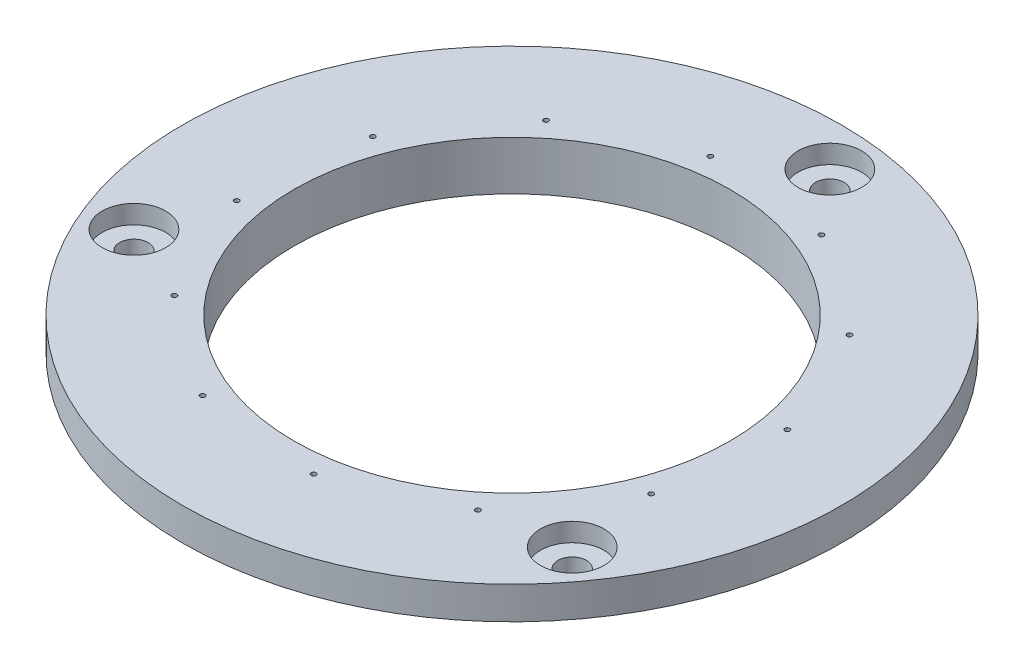
SolidWorks part; units mm, degrees
ref_plane "Front Plane" through (0, 0, 0) normal (0, 0, 1) x (1, 0, 0)
ref_plane "Top Plane" through (0, 0, 0) normal (0, 1, 0) x (1, 0, 0)
ref_plane "Right Plane" through (0, 0, 0) normal (1, 0, 0) x (0, 0, -1)
sketch "Sketch2" plane through (0, 0, 0) normal (0, 1, 0) x (1, 0, 0)
  circle A0 centre (0, 0) radius 63.5
  circle A1 centre (0, 0) radius 42
  dimension "D1" = 127
  dimension "D2" = 84
extrude "Boss-Extrude1" add sketch "Sketch2" along normal blind 9.45
sketch "Sketch15" plane through (0, 9.45, 0) normal (0, 1, 0) x (1, 0, 0)
  line L1 (6.244, 55) -> (-50.7534, -22.0925)
  line L2 (-50.7534, -22.0925) -> (44.5094, -32.9075)
  line L3 (44.5094, -32.9075) -> (6.244, 55)
  circle A0 centre (0, 0) radius 27.6766 construction
hole_wizard "CBORE for M5 Hex Head Bolt1" positions "3DSketch8" profile "Sketch16" counterbore size "M5" standard "ANSI Metric"
sketch3d "3DSketch8"
  point P0 (6.244, 9.45, -55)
  point P3 (44.5094, 9.45, 32.9075)
  point P6 (-50.7534, 9.45, 22.0925)
sketch "Sketch16" plane through (6.244, 9.45, -55) normal (1, 0, 0) x (0, 0, 1)
  line L0 (0, 0) -> (0, 21.4024)
  line L1 (0, 21.4024) -> (2.75, 19.75)
  line L2 (2.75, 19.75) -> (2.75, 3.58)
  line L3 (2.75, 3.58) -> (6.12, 3.58)
  line L4 (6.12, 3.58) -> (6.12, 0)
  line L5 (6.12, 0) -> (0, 0)
  line L10 (0, 21.4024) -> (-2.75, 19.75) construction
  line L11 (0, -6.35) -> (0, 107.95) construction
  dimension "Hole Dia." = 5.5
  dimension "Hole Depth" = 19.75
  dimension "C'Bore Dia." = 12.24
  dimension "C'Bore Depth" = 3.58
  dimension "Drill Angle" = 118
sketch "Sketch26" plane through (0, 0, 0) normal (0, 1, 0) x (1, 0, 0)
  circle A0 centre (0, 0) radius 63.5
  dimension "D1" = 127
ref_axis "Axis1" through (0, 9.45, 0) along (0, -1, 0)
sketch "Sketch27" plane through (0, 0, 0) normal (0, 0, 1) x (1, 0, 0)
  line L0 (63.5, 0) -> (-63.5, 0) construction
  line L1 (63.5, 0) -> (58.5912, 0)
  line L2 (63.5, 0) -> (63.5, 3.175)
  line L3 (63.5, 3.175) -> (58.5912, 3.175)
  line L4 (58.5912, 0) -> (58.5912, 3.175)
  line L5 (69.85, 0) -> (-69.85, 0) construction
  line L6 (63.5, 0) -> (63.5, 9.45) construction
  line L7 (63.5, 0) -> (63.5, 9.45)
  line L8 (0, 9.45) -> (0, 0) construction
  line L9 (0, 0) -> (0, 15.4643) construction
  dimension "D1" = 117.1823
  dimension "D2" = 3.175
revolve "Cut-Revolve1" cut sketch "Sketch27" angle 360 about L9 region at (61.0456, 1.5875, 0)
hole_wizard "M1.2x0.25 Tapped Hole1" positions "Sketch28" profile "Sketch29" tap size "M1.2x0.25" standard "ANSI Metric" end condition through all
sketch "Sketch28" plane through (-17.102, 9.45, -64.2994) normal (0, 1, 0) x (0.108, 0, -0.9941)
  point P0 (-95.0061, 8.4911)
  point P3 (-74.3741, 20.6104)
  point P6 (-50.4466, 20.79)
  point P9 (-29.6349, 8.9817)
  point P12 (-17.5156, -11.6503)
  point P15 (-17.3361, -35.5778)
  point P18 (-29.1443, -56.3895)
  point P21 (-49.7764, -68.5087)
  point P24 (-73.7039, -68.6883)
  point P27 (-94.5155, -56.8801)
  point P30 (-106.6348, -36.248)
  point P33 (-106.8144, -12.3205)
sketch "Sketch29" plane through (-35.8084, 9.45, 29.2331) normal (1, 0, 0) x (0, 0, 1)
  line L0 (0, 0) -> (0, 9.45)
  line L1 (0, 9.45) -> (0.475, 9.45)
  line L2 (0.475, 9.45) -> (0.475, 0)
  line L3 (0.475, 0) -> (0, 0)
  line L4 (0, -6.35) -> (0, 107.95) construction
  dimension "Thru Tap Drill Dia." = 0.95
  dimension "Thru Tap Drill Depth" = 9.45
cosmetic thread "Hole Thread1" parameters "D2"=1.2
cosmetic thread "Hole Thread2" parameters "D2"=1.2
cosmetic thread "Hole Thread3" parameters "D2"=1.2
cosmetic thread "Hole Thread4" parameters "D2"=1.2
cosmetic thread "Hole Thread5" parameters "D2"=1.2
cosmetic thread "Hole Thread6" parameters "D2"=1.2
cosmetic thread "Hole Thread7" parameters "D2"=1.2
cosmetic thread "Hole Thread8" parameters "D2"=1.2
cosmetic thread "Hole Thread9" parameters "D2"=1.2
cosmetic thread "Hole Thread10" parameters "D2"=1.2
cosmetic thread "Hole Thread11" parameters "D2"=1.2
cosmetic thread "Hole Thread12" parameters "D2"=1.2
equation "\"ODia\"= 5in"
equation "\"IDiam\"= 84mm"
equation "\"Thick\"= 9.45mm"
equation "\"Lip\"= 3.29mm"
equation "\"D1@Boss-Extrude1\"=\"Thick\""
